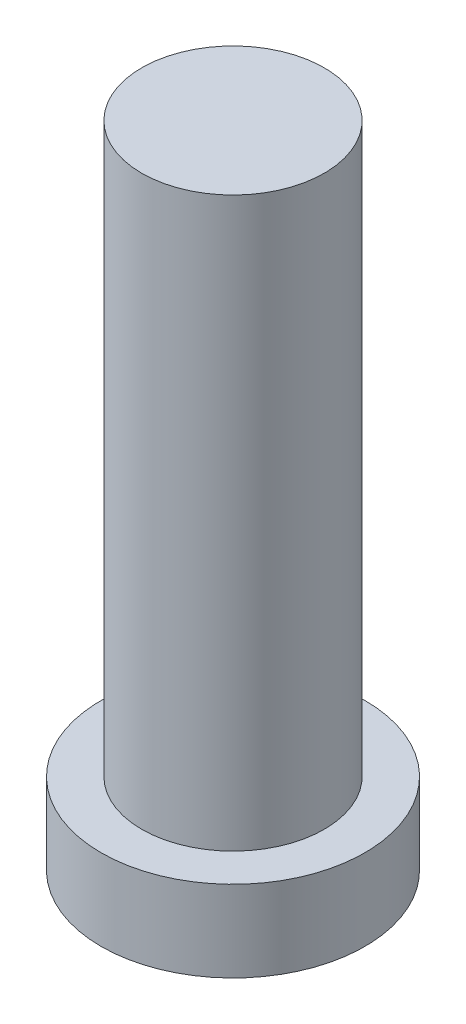
SolidWorks part; units mm, degrees
ref_plane "Front Plane" through (0, 0, 0) normal (0, 0, 1) x (1, 0, 0)
ref_plane "Top Plane" through (0, 0, 0) normal (0, 1, 0) x (1, 0, 0)
ref_plane "Right Plane" through (0, 0, 0) normal (1, 0, 0) x (0, 0, -1)
sketch "Sketch2" plane through (0, 0, 0) normal (0, 1, 0) x (1, 0, 0)
  circle A0 centre (0, 0) radius 2.25
  circle A1 centre (0, 0) radius 3.25
  dimension "D1" = 4.5
  dimension "D2" = 6.5
extrude "Boss-Extrude1" add sketch "Sketch2" along normal blind 14 contours A0 region at (0, 0, 0)
extrude "Boss-Extrude2" add sketch "Sketch2<3>" against normal blind 2 contours A1 A0 | A0 region at (0, 0, 0) region at (-3.1581, 0, 0)
sketch "Sketch2<3>" plane through (0, 0, 0) normal (0, 1, 0) x (1, 0, 0) same geometry as "Sketch2"
